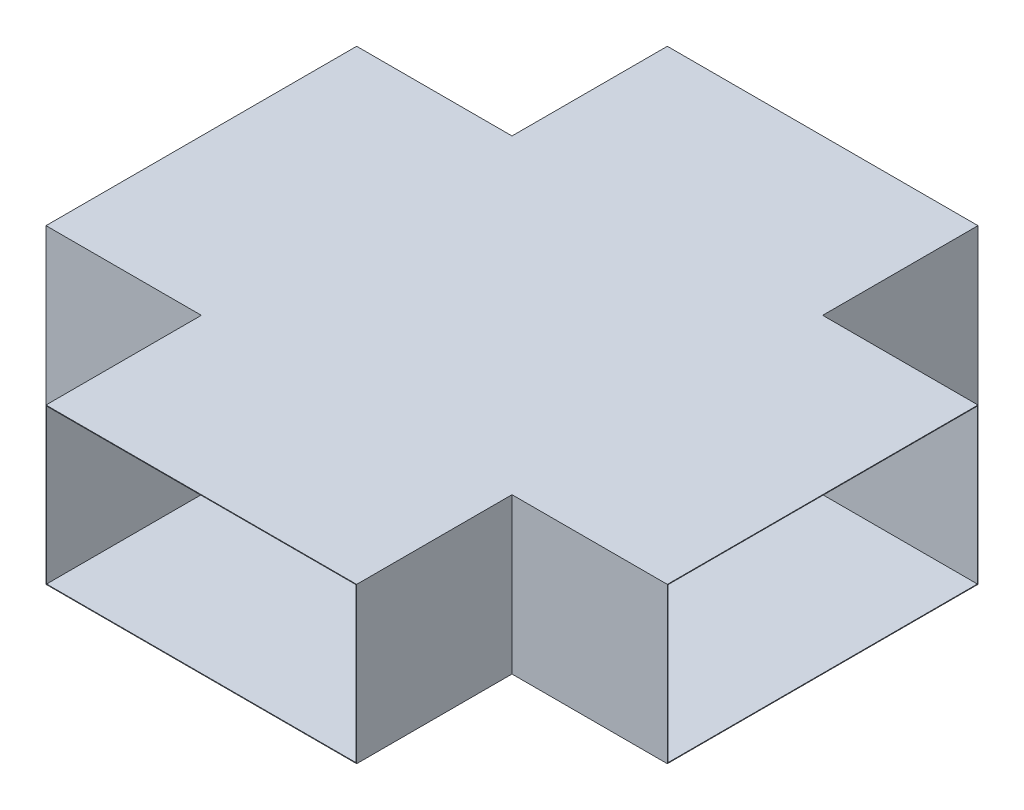
SolidWorks part; units mm, degrees
material "Plain Carbon Steel"
ref_plane "Front Plane" through (0, 0, 0) normal (0, 0, 1) x (1, 0, 0)
ref_plane "Top Plane" through (0, 0, 0) normal (0, 1, 0) x (1, 0, 0)
ref_plane "Right Plane" through (0, 0, 0) normal (1, 0, 0) x (0, 0, -1)
sketch "Sketch1" plane through (0, 0, 0) normal (1, 0, 0) x (0, 0, -1)
  line L0 (-500, 250) -> (500, -250) construction
  line L1 (-500, 250) -> (500, 250)
  line L2 (-500, 250) -> (-500, -250)
  line L3 (-500, -250) -> (500, -250)
  line L4 (500, 250) -> (500, -250)
  line L5 (-500, -250) -> (500, 250) construction
  dimension "Width" = 1000
  dimension "Height" = 500
extrude "Extrude-Thin1" add sketch "Sketch1" along normal mid plane 2000 thin thin type one direction reverse wall 2
sketch "Sketch2" plane through (0, -250, 500) normal (0, 0, -1) x (1, 0, 0)
  line L1 (-500, 0) -> (500, 0)
  line L2 (-500, 0) -> (-500, -500)
  line L3 (-500, -500) -> (500, -500)
  line L4 (500, 0) -> (500, -500)
  line L6 (-500, 0) -> (500, -500) construction
  line L7 (-500, -500) -> (500, 0) construction
  dimension "Width" = 1000
  dimension "Height" = 500
extrude "Extrude-Thin2" add sketch "Sketch2" against normal blind 500 thin thin type one direction reverse wall 2
sketch "Sketch3" plane through (0, -750, 1000) normal (0, 0, -1) x (1, 0, 0)
  line L0 (-498, -502) -> (-498, -998) construction
  line L1 (-498, -998) -> (498, -998) construction
  line L2 (498, -998) -> (498, -502) construction
  line L3 (498, -502) -> (-498, -502) construction
  line L4 (-498, -502) -> (-498, -998)
  line L5 (-498, -998) -> (498, -998)
  line L6 (498, -998) -> (498, -502)
  line L7 (498, -502) -> (-498, -502)
extrude "Cut-Extrude1" cut sketch "Sketch3" along normal up to next
mirror "Mirror1" about plane through (0, 0, 0) normal (0, 0, 1) of "Cut-Extrude1", "Extrude-Thin2"
sketch "Sketch4" plane through (0, 0, 0) normal (0, 1, 0) x (1, 0, 0)
  line L0 (498, -1000) -> (-498, -1000) construction
  line L1 (498, 1000) -> (-498, 1000) construction
  line L3 (1000, -498) -> (1000, 498) construction
  line L4 (-1000, -498) -> (-1000, 498) construction
  point P0 (1000, 0)
  point P1 (-1000, 0)
  point P2 (0, -1000)
  point P3 (0, 0)
  point P11 (0, 1000)
other "CPoint1" parameters "Diameter"=10, "StubLength"=500
ref_axis "Axis1" through (1010, 0, 0) along (-1, 0, 0)
other "CPoint2" parameters "Diameter"=10, "StubLength"=500
ref_axis "Axis2" through (-1010, 0, 0) along (1, 0, 0)
other "CPoint3" parameters "Diameter"=10, "StubLength"=500
ref_axis "Axis3" through (0, 0, 1010) along (0, 0, -1)
other "CPoint4" parameters "Diameter"=10, "StubLength"=500
ref_axis "Axis4" through (0, 0, -1010) along (0, 0, 1)
other "RPoint1"
equation "\"Thickness@Extrude-Thin2\" = \"Thickness@Extrude-Thin1\""
equation "\"D1@Extrude-Thin1\"=2 * \"Width@Sketch1\""
equation "\"D1@Extrude-Thin2\"=0.5 * \"Width@Sketch1\""
